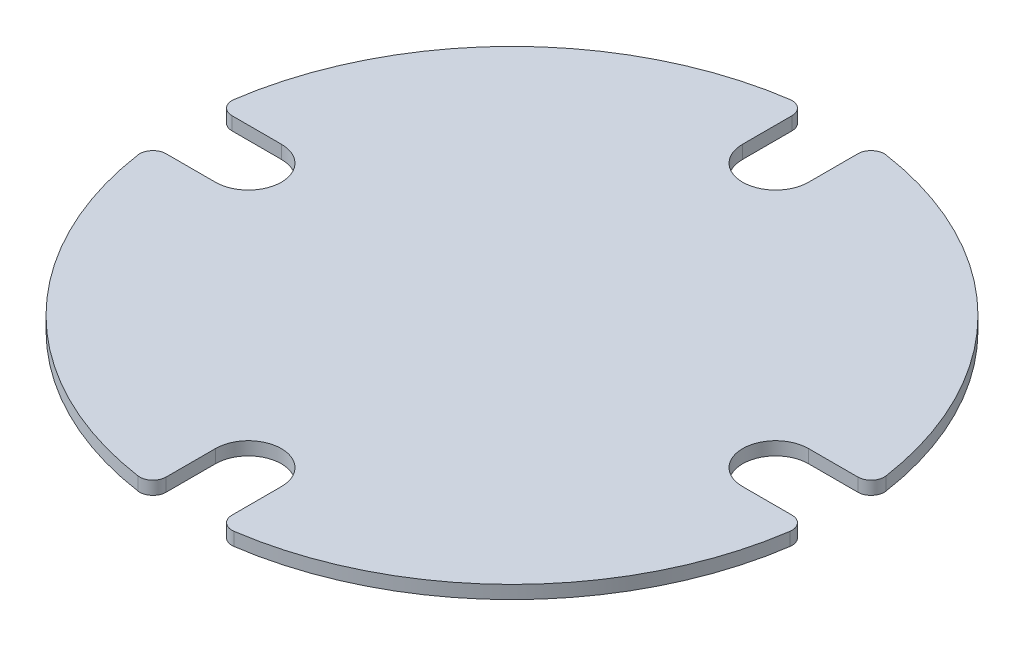
SolidWorks part; units mm, degrees
ref_plane "Front Plane" through (0, 0, 0) normal (0, 0, 1) x (1, 0, 0)
ref_plane "Top Plane" through (0, 0, 0) normal (0, 1, 0) x (1, 0, 0)
ref_plane "Right Plane" through (0, 0, 0) normal (1, 0, 0) x (0, 0, -1)
sketch "Sketch3" plane through (0, 0, 0) normal (0, 1, 0) x (1, 0, 0)
  circle A0 centre (0, 0) radius 63.5
  dimension "D1" = 127
extrude "Boss-Extrude1" add sketch "Sketch3" along normal blind 2.54
sketch "Sketch4" plane through (0, 2.54, 0) normal (0, 1, 0) x (1, 0, 0)
  line L2 (-6.35, 50.8) -> (-6.35, 63.5)
  line L3 (-6.35, 63.5) -> (6.35, 63.5)
  line L4 (6.35, 50.8) -> (6.35, 63.5)
  circle A2 centre (0, 0) radius 63.5 construction
  arc A3 (-6.35, 50.8) -> (6.35, 50.8) centre (0, 50.8) ccw
  point P0 (0, 63.5)
  dimension "D1" = 12.7
  dimension "D2" = 12.7
extrude "Cut-Extrude1" cut sketch "Sketch4" against normal up to next
fillet "Fillet1" radius 2.54 2 edges at (6.35, 1.27, -63.1817) (-6.35, 1.27, -63.1817)
pattern_circular "CirPattern1" count 4 over 360 about axis through (0, 2.54, 0) along (0, -1, 0) of "Cut-Extrude1", "Fillet1"
